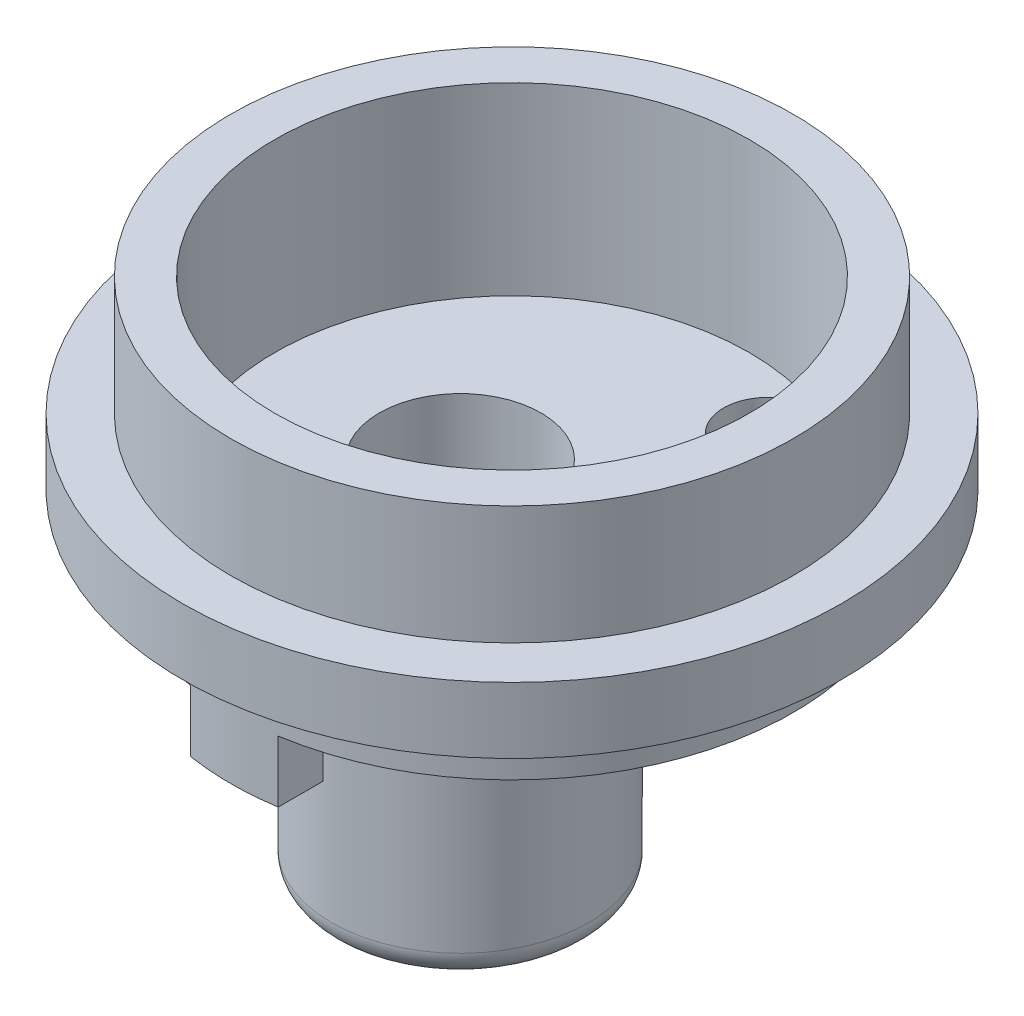
SolidWorks part; units mm, degrees
note: '?' marks a value the reader was unsure of.
ref_plane "Plane1" through (0, 0, 0) normal (0, 0, 1) x (1, 0, 0)
ref_plane "Plane2" through (0, 0, 0) normal (0, 1, 0) x (1, 0, 0)
ref_plane "Plane3" through (0, 0, 0) normal (1, 0, 0) x (0, 0, -1)
sketch "Sketch1" plane through (0, 0, 0) normal (0, 1, 0) x (1, 0, 0)
  circle A0 centre (0, 0) radius 8.128
  dimension "D1" = 16.256
extrude "Top Body" add sketch "Sketch1" along normal blind 6.858
sketch "Sketch2" plane through (0, 0, 0) normal (0, -1, 0) x (1, 0, 0)
  line L0 (50, 0) -> (-50, 0) construction
  line L1 (0, -50) -> (0, 50) construction
  circle A0 centre (-1.4986, 0) radius 5.08
  dimension "D2" = 10.16
  dimension "D1" = 1.4986
extrude "Eccentric Sleeve" add sketch "Sketch2" along normal blind 2.54
ref_axis "Axis1" through (-1.4986, -52.54, 0) along (0, 1, 0)?
sketch "Sketch3" plane through (0, 6.858, 0) normal (0, 1, 0) x (-1, 0, 0)
  circle A0 centre (1.4986, 0) radius 3.7247
  circle A1 centre (1.4986, 0) radius 5.08 construction
  dimension "D1" = 7.4493
extrude "Eccentric Shaft" add sketch "Sketch3" against normal blind 15.8242
ref_plane "Plane4" through (0, 1.524, 0) normal (0, -1, 0) x (1, 0, 0)
sketch "Sketch4" plane through (0, 1.524, 0) normal (0, -1, 0) x (1, 0, 0)
  circle A1 centre (0, 0) radius 9.525
  circle A2 centre (0, 0) radius 9.525
  dimension "D1" = 1.397
extrude "Flange" add sketch "Sketch4" against normal offset from surface (1.905 mm away) 3.429
sketch "Sketch5" plane through (0, 1.524, 0) normal (0, -1, 0) x (1, 0, 0)
  circle A0 centre (0, 0) radius 6.858
  dimension "D1" = 6.858
extrude "Top Hole" cut sketch "Sketch5" against normal through all
sketch "Sketch6" plane through (0, 0, 0) normal (0, 0, 1) x (1, 0, 0)
  line L0 (-1.4986, 5.3652) -> (-1.4986, -9.7324) construction
  line L1 (-1.4986, -52.54) -> (-1.4986, 197.46) construction
  line L2 (0.8382, 1.524) -> (-1.4986, 1.524)
  line L3 (9.525, 1.524) -> (-9.525, 1.524) construction
  line L4 (0.8382, 1.524) -> (0.8382, -3.81)
  line L5 (0.8382, -3.81) -> (0.4318, -6.8596)
  line L6 (0.4318, -6.8596) -> (0.4318, -8.9662)
  line L7 (2.2261, -8.9662) -> (-5.2233, -8.9662) construction
  line L8 (0.4318, -8.9662) -> (-1.4986, -8.9662)
  line L9 (-1.4986, -8.9662) -> (-1.4986, 1.524)
  point P14 (0.4318, -8.9662)
  point P15 (-3.429, -8.9662)
  point P16 (0.8382, -3.81)
  point P17 (-3.8354, -3.81)
  dimension "D1" = 3.0496
  dimension "D2" = 5.334
  dimension "D3" = 3.8608
  dimension "D4" = 4.6736
revolve "Tapped Hole" cut sketch "Sketch6" angle 360 about L0
sketch "Sketch7" plane through (0, 1.524, 0) normal (0, 1, 0) x (-1, 0, 0)
  circle A0 centre (0, 0) radius 6.858 construction
  arc A1 (-2.8053, 6.258) -> (-2.8053, -6.258) centre (0, 0) ccw
  circle A2 centre (1.4986, 0) radius 5.08 construction
  arc A3 (-1.5289, 4.0793) -> (-1.5289, -4.0793) centre (1.4986, 0) ccw
  arc A4 (-2.8053, -6.258) -> (-1.5289, -4.0793) centre (-2.2858, -5.0991) ccw
  arc A5 (-2.8053, 6.258) -> (-1.5289, 4.0793) centre (-2.2858, 5.0991) cw
  dimension "D1" = 1.27
extrude "Groove" cut sketch "Sketch7" against normal through all
sketch "Sketch8" plane through (0, 0, 0) normal (0, -1, 0) x (1, 0, 0)
  line L0 (-1.27, 8.0282) -> (-1.27, 6.7394)
  line L1 (1.27, 8.0282) -> (1.27, 6.7394)
  line L2 (1.27, -6.7394) -> (1.27, -8.0282)
  line L3 (-1.27, -6.7394) -> (-1.27, -8.0282)
  circle A0 centre (0, 0) radius 8.128 construction
  arc A1 (1.27, 8.0282) -> (-1.27, 8.0282) centre (0, 0) ccw
  arc A2 (-1.27, -6.7394) -> (1.27, -6.7394) centre (0, 0) ccw
  arc A3 (1.27, 6.7394) -> (-1.27, 6.7394) centre (0, 0) ccw
  arc A4 (2.8053, -6.258) -> (2.8053, 6.258) centre (0, 0) ccw construction
  arc A5 (-1.27, -8.0282) -> (1.27, -8.0282) centre (0, 0) ccw
  dimension "D1" = 2.54
extrude "Pins" add sketch "Sketch8" along normal blind 1.778
ref_axis "Axis2" through (-1.4986, -52.54, 0) along (0, 1, 0)?
fillet "Fillet1" radius 0.508 3 edges at (1.19, 0, -5.7411) (6.858, 0, 0) (1.19, 0, 5.7411)
fillet "Fillet2" radius 0.762 1 edges at (-1.4986, -8.9662, 3.7247)
